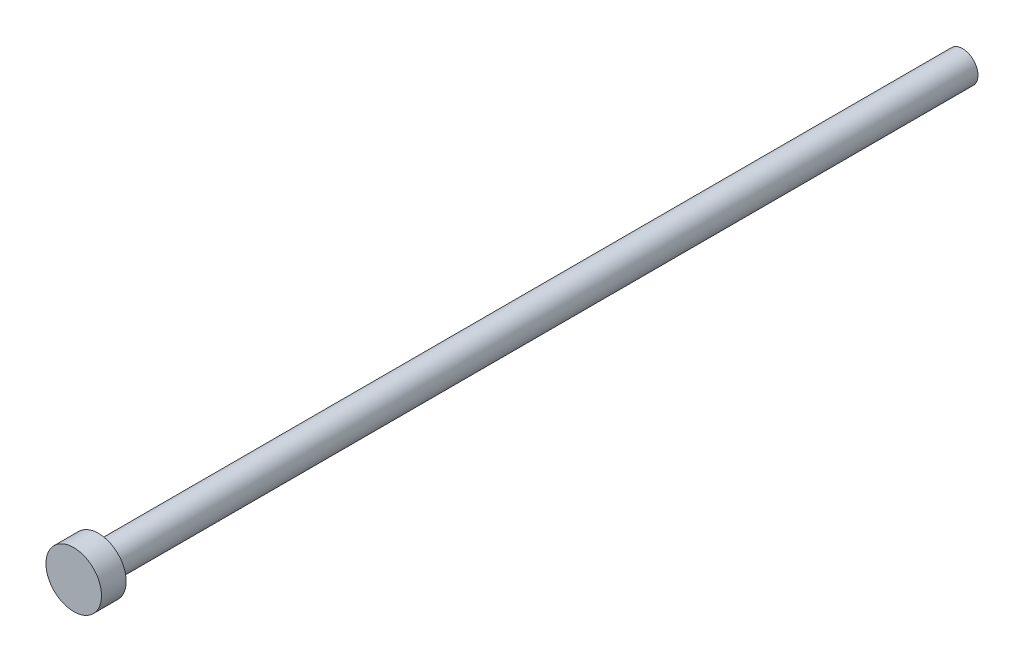
SolidWorks part; units mm, degrees
material "AISI 316 Annealed Stainless Steel Bar (SS)"
ref_plane "Front Plane" through (0, 0, 0) normal (0, 0, 1) x (1, 0, 0)
ref_plane "Top Plane" through (0, 0, 0) normal (0, 1, 0) x (1, 0, 0)
ref_plane "Right Plane" through (0, 0, 0) normal (1, 0, 0) x (0, 0, -1)
sketch "Extrude sketch 1" plane through (0, 0, 0) normal (0, 0, 1) x (1, 0, 0)
  circle A0 centre (-111, 111) radius 5
  dimension "D1" = 10
extrude "Extrude 1" add sketch "Extrude sketch 1" along normal blind 280 from offset 225 separate body
sketch "Extrude sketch 2" plane through (0, 0, 0) normal (0, 0, 1) x (1, 0, 0)
  circle A0 centre (-111, 111) radius 9
  dimension "D1" = 18
extrude "Extrude 2" add sketch "Extrude sketch 2" along normal blind 8 from offset 505 separate body
combine bodies "Combine (weld / assembly of features)" operation type add bodies to combine 102 101
